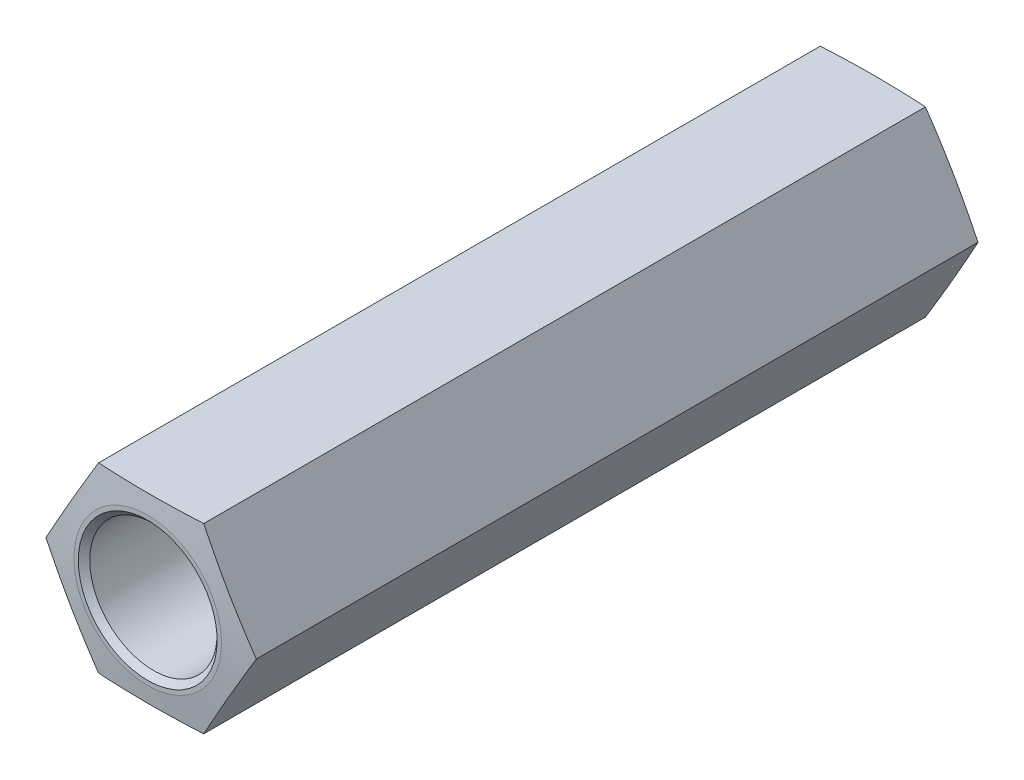
SolidWorks part; units mm, degrees
material "Plain Carbon Steel"
ref_plane "Front Plane" through (0, 0, 0) normal (0, 0, 1) x (1, 0, 0)
ref_plane "Top Plane" through (0, 0, 0) normal (0, 1, 0) x (1, 0, 0)
ref_plane "Right Plane" through (0, 0, 0) normal (1, 0, 0) x (0, 0, -1)
sketch "Sketch1" plane through (0, 0, 0) normal (0, 0, 1) x (1, 0, 0)
  line L0 (-3.6662, 0) -> (-1.8331, -3.175)
  line L1 (-1.8331, -3.175) -> (1.8331, -3.175)
  line L2 (1.8331, -3.175) -> (3.6662, 0)
  line L3 (3.6662, 0) -> (1.8331, 3.175)
  line L4 (1.8331, 3.175) -> (-1.8331, 3.175)
  line L5 (-1.8331, 3.175) -> (-3.6662, 0)
  line L6 (0, 3.175) -> (0, -3.175) construction
  line L7 (-2.7496, 1.5875) -> (0, 0) construction
  circle A0 centre (0, 0) radius 2.22
  point P2 (0, 0)
  dimension "D8" = 4.44
  dimension "D1" = 3.6662
  dimension "D2" = 3.6662
  dimension "D3" = 3.6662
  dimension "D4" = 3.175
  dimension "D5" = 6.35
  dimension "D6" = 7.3323
  dimension "D7" = 3.6662
extrude "Extrude1" add sketch "Sketch1" along normal mid plane 25.4
cosmetic thread "Cosmetic Thread1" parameters "D2"=5
chamfer "Chamfer1" distance 0.2 angle 45 2 edges at (2.22, 0, -12.7) (2.22, 0, 12.7)
ref_plane "Plane1" through (0, 0, 0) normal (0, 1, 0) x (-1, 0, 0)
sketch "Sketch2" plane through (0, 0, 0) normal (0, -1, 0) x (1, 0, 0)
  line L0 (-2.5727, -12.7) -> (-3.6662, -12.58)
  line L3 (-3.6662, -12.58) -> (-3.6662, -12.7)
  line L4 (-3.6662, -12.7) -> (-2.5727, -12.7)
  dimension "D1" = 1.0934
  dimension "D2" = 0.12
revolve "Cut-Revolve1" cut sketch "Sketch2" angle 360 about axis through (0, 0, 12.7) along (0, 0, -1)
mirror "Mirror1" about plane through (0, 0, 0) normal (0, 0, 1) of "Cut-Revolve1"
ref_axis "Axis1" through (0, 0, -14.6674) along (0, 0, 1)
ref_plane "Plane2" through (0, 0, 13.87) normal (0, 0, 1) x (1, 0, 0)
ref_plane "Plane3" through (0, 0, -12.82) normal (0, 0, 1) x (1, 0, 0)
